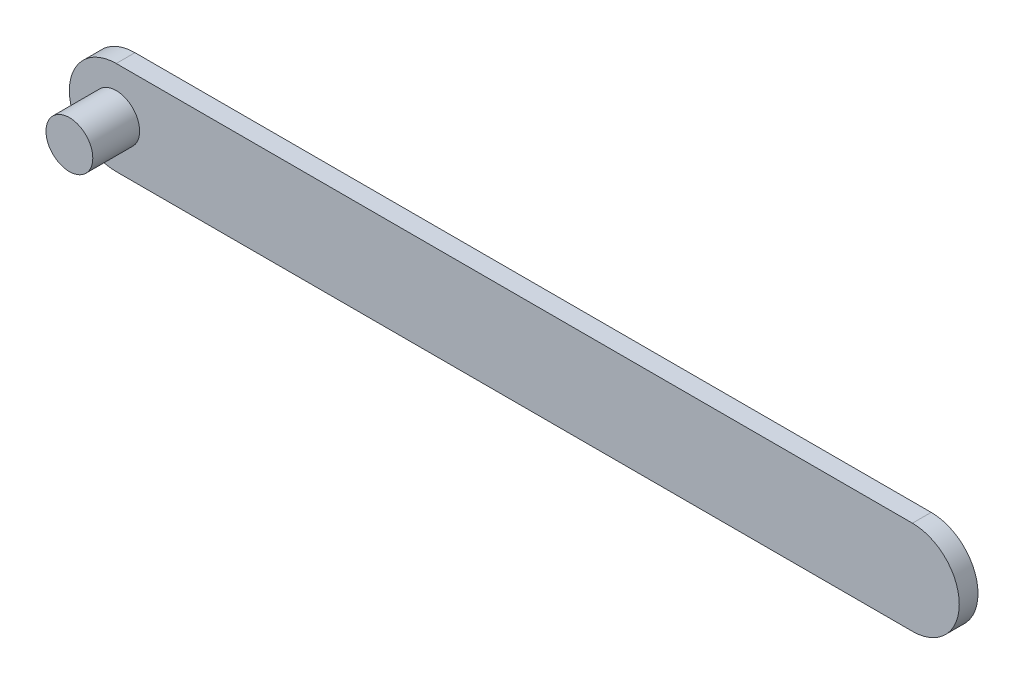
SolidWorks part; units mm, degrees
ref_plane "前视基准面" through (0, 0, 0) normal (0, 0, 1) x (1, 0, 0)
ref_plane "上视基准面" through (0, 0, 0) normal (0, 1, 0) x (1, 0, 0)
ref_plane "右视基准面" through (0, 0, 0) normal (1, 0, 0) x (0, 0, -1)
other "Configuration Table"
sketch "Sketch1" plane through (0, 0, 0) normal (0, 0, 1) x (1, 0, 0)
  line L1 (0, 0) -> (85, 0)
  line L3 (0, 10) -> (85, 10)
  arc A0 (0, 10) -> (0, 0) centre (0, 5) ccw
  arc A1 (85, 0) -> (85, 10) centre (85, 5) ccw
  dimension "D1" = 85
  dimension "D2" = 10
extrude "Boss-Extrude1" add sketch "Sketch1" along normal blind 2
sketch "Sketch2" plane through (0, 0, 2) normal (0, 0, 1) x (1, 0, 0)
  circle A0 centre (0, 5) radius 2.5
  dimension "D1" = 5
extrude "Boss-Extrude2" add sketch "Sketch2" along normal blind 5
